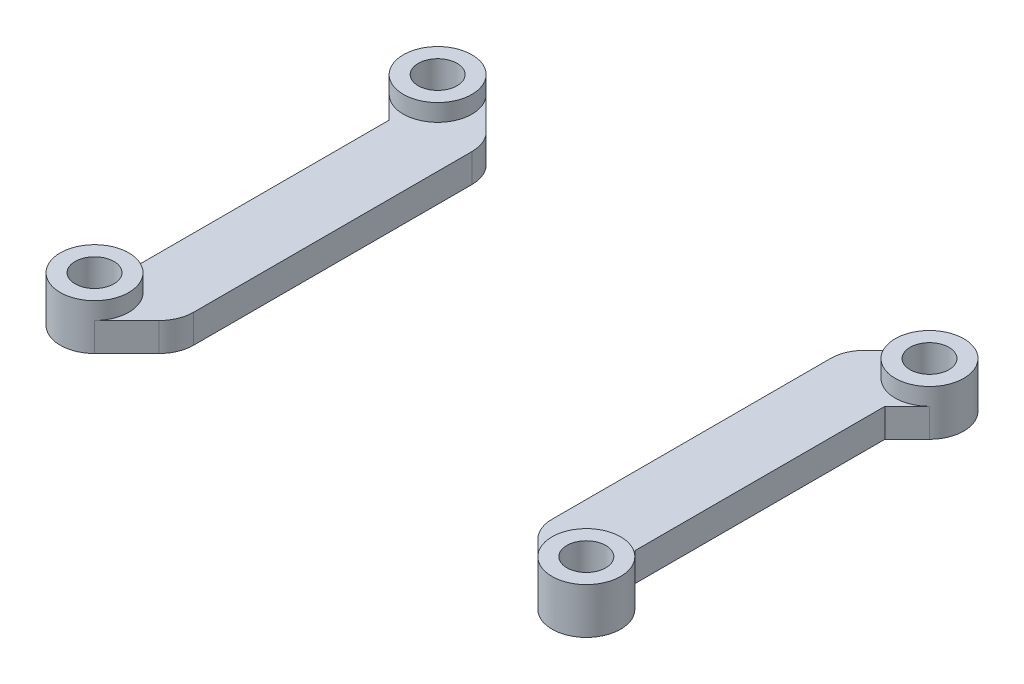
SolidWorks part; units mm, degrees
ref_plane "Front Plane" through (0, 0, 0) normal (0, 0, 1) x (1, 0, 0)
ref_plane "Top Plane" through (0, 0, 0) normal (0, 1, 0) x (1, 0, 0)
ref_plane "Right Plane" through (0, 0, 0) normal (1, 0, 0) x (0, 0, -1)
sketch "Sketch1" plane through (0, 0, 0) normal (0, 1, 0) x (1, 0, 0)
  line L1 (-21.5, 15) -> (21.5, 15) construction
  line L2 (-21.5, 15) -> (-21.5, -15) construction
  line L3 (-21.5, -15) -> (21.5, -15) construction
  line L4 (21.5, 15) -> (21.5, -15) construction
  line L5 (-21.5, 15) -> (21.5, -15) construction
  line L6 (-21.5, -15) -> (21.5, 15) construction
  circle A0 centre (-21.5, 15) radius 1.7
  circle A1 centre (21.5, 15) radius 1.7
  circle A2 centre (21.5, -15) radius 1.7
  circle A3 centre (-21.5, -15) radius 1.7
  circle A4 centre (-21.5, 15) radius 3
  circle A5 centre (-21.5, -15) radius 3
  circle A6 centre (21.5, -15) radius 3
  circle A7 centre (21.5, 15) radius 3
  point P0 (0, 0)
  point P14 (0, 0)
  dimension "D3" = 3.4
  dimension "D4" = 6
  dimension "D1" = 43
  dimension "D2" = 30
extrude "Boss-Extrude1" add sketch "Sketch1" along normal blind 4
sketch "Sketch2" plane through (0, 0, 0) normal (0, 1, 0) x (1, 0, 0)
  line L0 (-21.5, 15) -> (-18.6716, 12.1716) construction
  line L1 (-19.3787, 17.1213) -> (-16.5503, 14.2929)
  line L2 (-23.6213, 12.8787) -> (-21.6716, 10.9289)
  line L3 (-21.5, -15) -> (-18.6716, -12.1716) construction
  line L4 (-23.6213, -12.8787) -> (-21.6716, -10.9289)
  line L5 (-19.3787, -17.1213) -> (-16.5503, -14.2929)
  line L6 (-18.6716, 12.1716) -> (-18.6716, -12.1716) construction
  line L7 (-15.6716, 12.1716) -> (-15.6716, -12.1716)
  line L8 (-21.6716, 10.9289) -> (-21.6716, -10.9289)
  line L9 (0, -1000) -> (0, 49000) construction
  line L10 (18.6716, 12.1716) -> (18.6716, -12.1716) construction
  line L11 (21.5, -15) -> (18.6716, -12.1716) construction
  line L12 (21.5, 15) -> (18.6716, 12.1716) construction
  line L13 (21.6716, 10.9289) -> (21.6716, -10.9289)
  line L14 (15.6716, 12.1716) -> (15.6716, -12.1716)
  line L15 (19.3787, -17.1213) -> (16.5503, -14.2929)
  line L16 (23.6213, -12.8787) -> (21.6716, -10.9289)
  line L17 (23.6213, 12.8787) -> (21.6716, 10.9289)
  line L18 (19.3787, 17.1213) -> (16.5503, 14.2929)
  arc A0 (-19.3787, 17.1213) -> (-23.6213, 12.8787) centre (-21.5, 15) ccw
  circle A2 centre (-21.5, 15) radius 3 construction
  arc A3 (-23.6213, -12.8787) -> (-19.3787, -17.1213) centre (-21.5, -15) ccw
  arc A4 (-16.5503, -14.2929) -> (-15.6716, -12.1716) centre (-18.6716, -12.1716) ccw
  circle A5 centre (-21.5, -15) radius 3 construction
  arc A6 (-15.6716, 12.1716) -> (-16.5503, 14.2929) centre (-18.6716, 12.1716) ccw
  arc A7 (-16.5503, -14.2929) -> (-15.6716, -12.1716) centre (-18.6716, -12.1716) ccw
  arc A8 (-15.6716, 12.1716) -> (-16.5503, 14.2929) centre (-18.6716, 12.1716) ccw
  arc A9 (15.6716, 12.1716) -> (16.5503, 14.2929) centre (18.6716, 12.1716) cw
  arc A10 (16.5503, -14.2929) -> (15.6716, -12.1716) centre (18.6716, -12.1716) cw
  arc A11 (15.6716, 12.1716) -> (16.5503, 14.2929) centre (18.6716, 12.1716) cw
  arc A12 (16.5503, -14.2929) -> (15.6716, -12.1716) centre (18.6716, -12.1716) cw
  arc A13 (23.6213, -12.8787) -> (19.3787, -17.1213) centre (21.5, -15) cw
  arc A14 (19.3787, 17.1213) -> (23.6213, 12.8787) centre (21.5, 15) cw
  point P2 (-20.0858, 13.5858)
  point P13 (-20.0858, -13.5858)
  point P20 (-18.6716, 0)
  point P41 (18.6716, 0)
  point P42 (20.0858, -13.5858)
  point P43 (20.0858, 13.5858)
  dimension "D1" = 45
  dimension "D2" = 45
  dimension "D3" = 4
  dimension "D4" = 4
  dimension "D5" = 3
  dimension "D6" = 3
extrude "Boss-Extrude2" add sketch "Sketch2" along normal blind 2.5 contours L7 A6 L1 A0 L2 L8 L4 A3 L5 A4 | A14 L18 A9 L14 A10 L15 A13 L16 L13 L17 region at (-19.3328, 0, 0) region at (19.3328, 0, 0)
extrude "Cut-Extrude1" cut sketch "Sketch1<2>" against normal through all both and the other way through all contours A3 | A0 | A1 | A2 region at (-21.5, 0, -15) region at (21.5, 0, -15) region at (21.5, 0, 15) region at (-21.5, 0, 15)
sketch "Sketch1<2>" plane through (0, 0, 0) normal (0, 1, 0) x (1, 0, 0) same geometry as "Sketch1"
